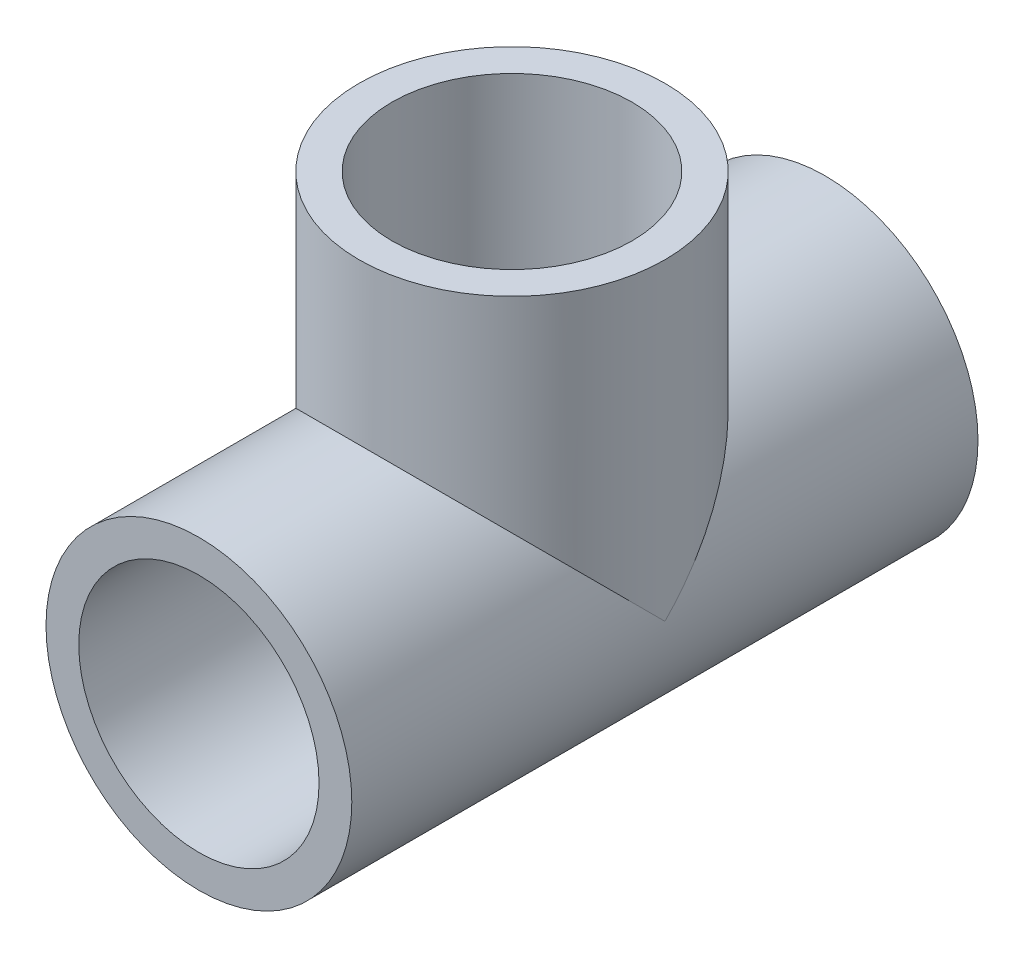
SolidWorks part; units mm, degrees
ref_plane "Front Plane" through (0, 0, 0) normal (0, 0, 1) x (1, 0, 0)
ref_plane "Top Plane" through (0, 0, 0) normal (0, 1, 0) x (1, 0, 0)
ref_plane "Right Plane" through (0, 0, 0) normal (1, 0, 0) x (0, 0, -1)
sketch "Sketch1" plane through (0, 0, 0) normal (0, 1, 0) x (1, 0, 0)
  line L0 (16.6687, 34.1313) -> (0, 34.1313)
  line L1 (0, 34.1313) -> (0, -34.1313)
  line L2 (0, -34.1313) -> (16.6687, -34.1313)
  line L3 (16.6687, -34.1313) -> (16.6687, 34.1313)
  line L4 (0, -118.244) -> (0, 82.7642) construction
  dimension "D1" = 68.2625
  dimension "D2" = 16.6687
revolve "Revolve1" add sketch "Sketch1" angle 360 about L4 reverse direction yes
sketch "Sketch2" plane through (0, 0, 0) normal (0, 0, 1) x (1, 0, 0)
  line L0 (0, 34.1313) -> (-16.6687, 34.1313)
  line L1 (-16.6687, 34.1313) -> (-16.6687, 0)
  line L2 (-16.6687, 0) -> (0, 0)
  line L3 (0, 0) -> (0, 34.1313)
  line L4 (0, 0) -> (0, 34.1313) construction
  line L5 (0, 0) -> (0, -16.6687) construction
  circle A0 centre (0, 0) radius 16.6687 construction
  dimension "D1" = 50.8
revolve "Revolve2" add sketch "Sketch2" angle 360 about L4 reverse direction yes
sketch "Sketch7" plane through (0, 0, 34.1313) normal (0, 0, 1) x (1, 0, 0)
  circle A0 centre (0, 0) radius 12.7
  dimension "D1" = 25.4
extrude "Cut-Extrude1" cut sketch "Sketch7" against normal through all
sketch "Sketch8" plane through (0, 34.1313, 0) normal (0, 1, 0) x (1, 0, 0)
  circle A0 centre (0, 0) radius 12.7
  dimension "D1" = 25.4
extrude "Cut-Extrude2" cut sketch "Sketch8" against normal up to next
sketch "Sketch9" plane through (0, 0, 34.1313) normal (0, 0, 1) x (1, 0, 0)
  circle A0 centre (0, 0) radius 13.0969
  dimension "D1" = 26.1937
extrude "Cut-Extrude3" cut sketch "Sketch9" against normal blind 19.05 contours A0
sketch "Sketch10" plane through (0, 0, -34.1313) normal (0, 0, -1) x (-1, 0, 0)
  circle A0 centre (0, 0) radius 13.0969
  dimension "D1" = 26.1937
extrude "Cut-Extrude4" cut sketch "Sketch10" against normal blind 19.05
sketch "Sketch11" plane through (0, 34.1313, 0) normal (0, 1, 0) x (1, 0, 0)
  circle A0 centre (0, 0) radius 13.0969
  dimension "D1" = 26.1937
extrude "Cut-Extrude5" cut sketch "Sketch11" against normal blind 19.05
